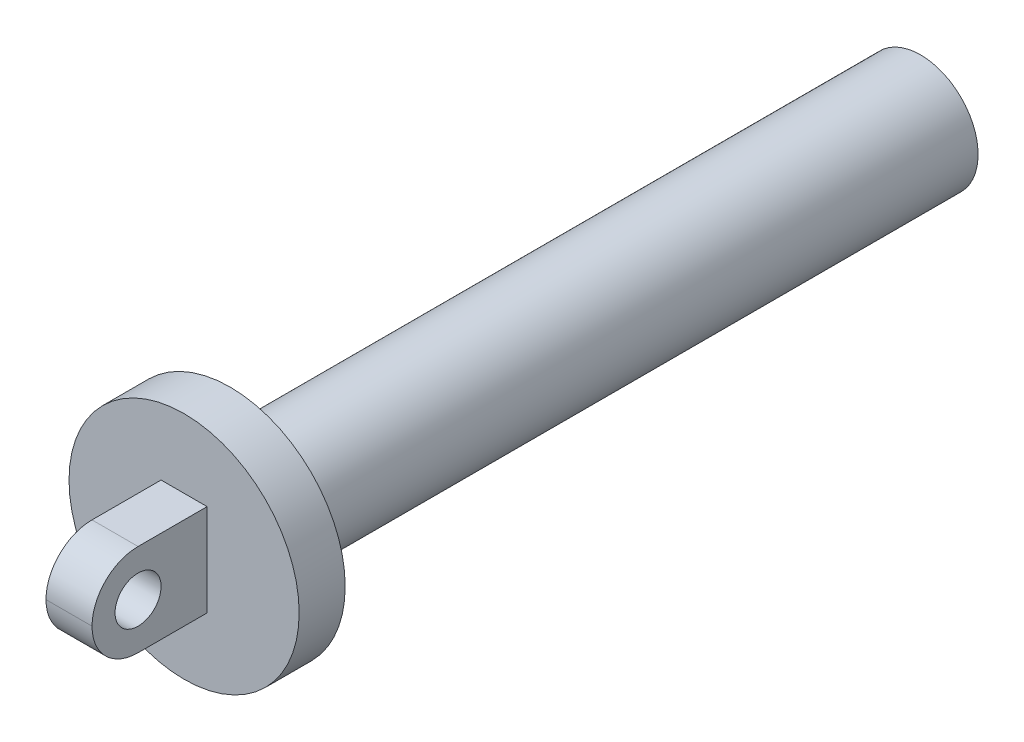
SolidWorks part; units mm, degrees
ref_plane "Front Plane" through (0, 0, 0) normal (0, 0, 1) x (1, 0, 0)
ref_plane "Top Plane" through (0, 0, 0) normal (0, 1, 0) x (1, 0, 0)
ref_plane "Right Plane" through (0, 0, 0) normal (1, 0, 0) x (0, 0, -1)
sketch "Sketch2" plane through (0, 0, 0) normal (0, 0, 1) x (1, 0, 0)
  circle A0 centre (0, 0) radius 25
  dimension "1" = 50
extrude "Boss-Extrude2" add sketch "Sketch2" along normal blind 10
sketch "Sketch3" plane through (0, 0, 10) normal (0, 0, 1) x (1, 0, 0)
  line L1 (-5, 10) -> (5, 10)
  line L2 (-5, 10) -> (-5, -10)
  line L3 (-5, -10) -> (5, -10)
  line L4 (5, 10) -> (5, -10)
  line L5 (-5, 10) -> (5, -10) construction
  line L6 (-5, -10) -> (5, 10) construction
  point P0 (0, 0)
  dimension "D1" = 20
  dimension "D2" = 10
extrude "Boss-Extrude3" add sketch "Sketch3" along normal blind 25
sketch "Sketch4" plane through (-5, 0, 0) normal (-1, 0, 0) x (0, 0, 1)
  line L0 (35, 10) -> (35, -10) construction
  line L1 (35, -10) -> (10, -10) construction
  circle A0 centre (25, 0) radius 5
  dimension "D1" = 10
  dimension "D2" = 10
  dimension "D3" = 10
extrude "Cut-Extrude1" cut sketch "Sketch4" against normal blind 20
fillet "Fillet1" radius 10 2 edges at (0, -10, 35) (0, 10, 35)
sketch "Sketch5" plane through (0, 0, 0) normal (0, 0, -1) x (-1, 0, 0)
  circle A0 centre (0, 0) radius 12.5
extrude "Boss-Extrude4" add sketch "Sketch5" along normal blind 150
